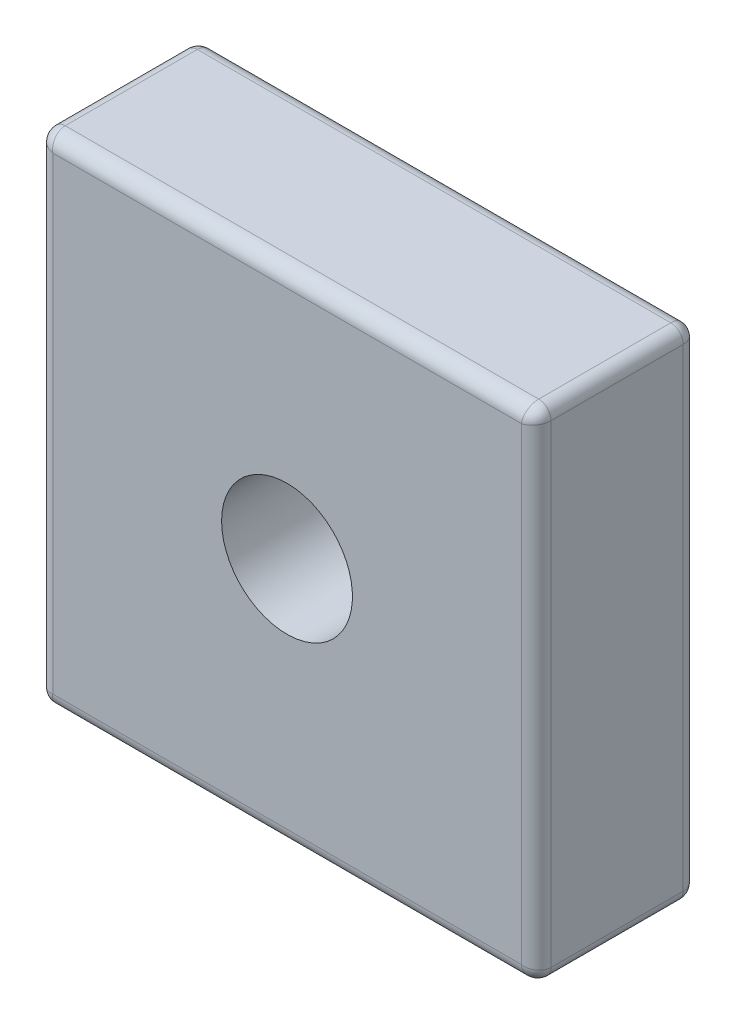
SolidWorks part; units mm, degrees
ref_plane "Front Plane" through (0, 0, 0) normal (0, 0, 1) x (1, 0, 0)
ref_plane "Top Plane" through (0, 0, 0) normal (0, 1, 0) x (1, 0, 0)
ref_plane "Right Plane" through (0, 0, 0) normal (1, 0, 0) x (0, 0, -1)
sketch "Sketch1" plane through (0, 0, 0) normal (0, 0, 1) x (1, 0, 0)
  line L1 (-19, 20) -> (19, 20)
  line L2 (-20, 19) -> (-20, -19)
  line L3 (-19, -20) -> (19, -20)
  line L4 (20, 19) -> (20, -19)
  line L5 (-20, 20) -> (20, -20) construction
  line L6 (-20, -20) -> (20, 20) construction
  circle A0 centre (0, 0) radius 5.25
  arc A1 (-20, -19) -> (-19, -20) centre (-19, -19) ccw
  arc A2 (19, -20) -> (20, -19) centre (19, -19) ccw
  arc A3 (19, 20) -> (20, 19) centre (19, 19) cw
  arc A4 (-19, 20) -> (-20, 19) centre (-19, 19) ccw
  point P0 (0, 0)
  dimension "D2" = 10.5
  dimension "D3" = 1
  dimension "D1" = 40
extrude "Boss-Extrude1" add sketch "Sketch1" along normal blind 13
fillet "Fillet1" radius 1.2 16 edges at (-19.7071, 19.7071, 0) (0, 20, 0) (19.7071, 19.7071, 0) (20, 0, 0) (19.7071, -19.7071, 0) (0, -20, 0) (-19.7071, -19.7071, 0) (-19.7071, 19.7071, 13) (0, 20, 13) (19.7071, 19.7071, 13) (20, 0, 13) (19.7071, -19.7071, 13) (0, -20, 13) (-19.7071, -19.7071, 13) (-20, 0, 0) (-20, 0, 13)
